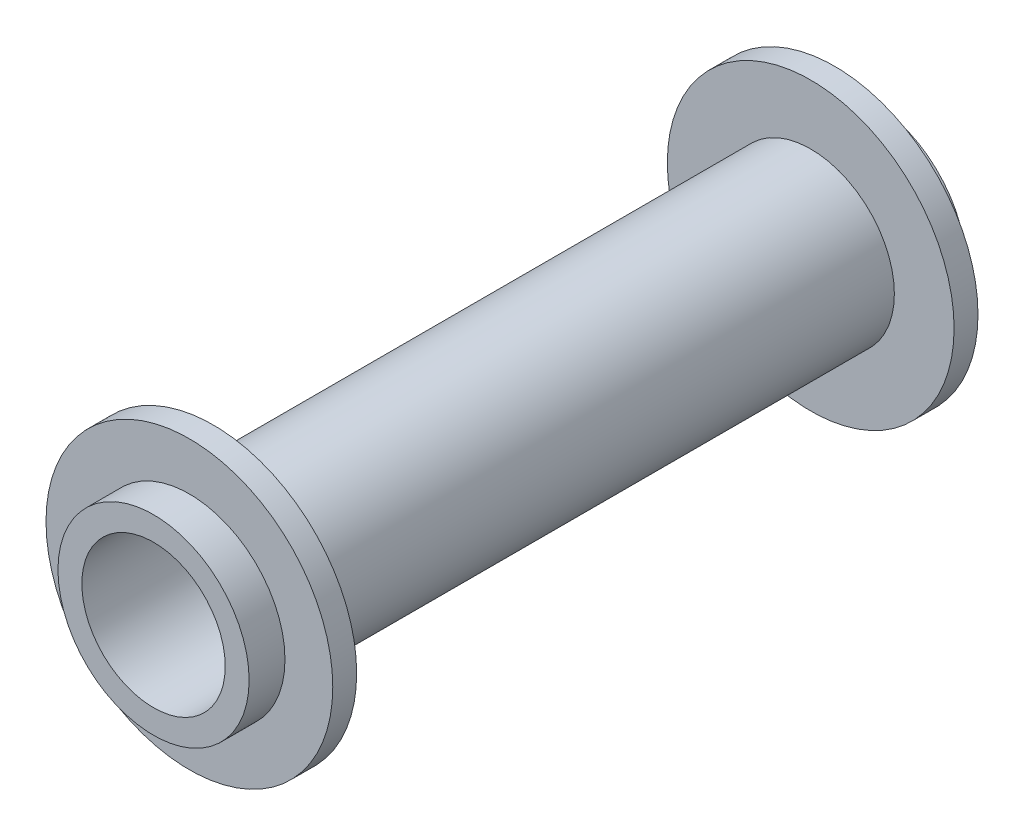
SolidWorks part; units mm, degrees
material "POM Acetal Copolymer"
ref_plane "Front Plane" through (0, 0, 0) normal (0, 0, 1) x (1, 0, 0)
ref_plane "Top Plane" through (0, 0, 0) normal (0, 1, 0) x (1, 0, 0)
ref_plane "Right Plane" through (0, 0, 0) normal (1, 0, 0) x (0, 0, -1)
sketch "Sketch2" plane through (0, 0, 0) normal (1, 0, 0) x (0, 0, -1)
  line L0 (0, 0) -> (56.7425, 0) construction
  line L1 (0, 6) -> (0, 8)
  line L2 (5, 7) -> (5, 12)
  line L3 (5, 12) -> (3, 12)
  line L4 (3, 12) -> (3, 8)
  line L5 (3, 8) -> (0, 8)
  line L6 (5, 7) -> (55, 7)
  line L7 (55, 7) -> (55, 12)
  line L8 (55, 12) -> (57, 12)
  line L9 (57, 12) -> (57, 8)
  line L10 (57, 8) -> (60, 8)
  line L11 (60, 8) -> (60, 6)
  line L12 (60, 6) -> (0, 6)
  dimension "D1" = 12
  dimension "D2" = 2
  dimension "D3" = 2
  dimension "D4" = 1
  dimension "D5" = 50
  dimension "D6" = 6
  dimension "D8" = 3
revolve "Revolve1" add sketch "Sketch2" angle 360 about L0
